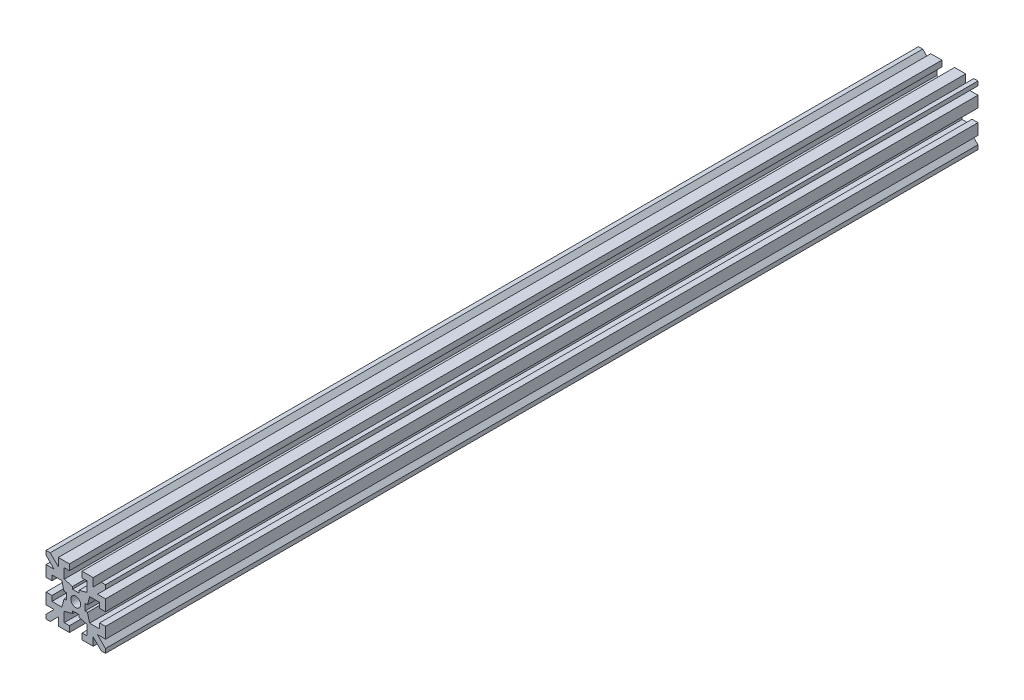
SolidWorks part; units mm, degrees
material "3.0205 (EN-AW 1200)"
ref_plane "Plano frontal" through (0, 0, 0) normal (0, 0, 1) x (1, 0, 0)
ref_plane "Plano superior" through (0, 0, 0) normal (0, 1, 0) x (1, 0, 0)
ref_plane "Plano direito" through (0, 0, 0) normal (1, 0, 0) x (0, 0, -1)
sketch "Esboço1" plane through (0, 0, 0) normal (0, 0, 1) x (1, 0, 0)
  line L0 (-25.7554, 0) -> (0, 0) construction
  line L1 (0, 0) -> (0, 21.5914) construction
  line L2 (0, 2.35) -> (-0.825, 2.35)
  line L3 (-0.825, 2.35) -> (-0.825, 2.95)
  line L4 (-0.825, 2.95) -> (-2.9, 3.5)
  line L5 (-2.9, 3.5) -> (-2.9, 6)
  line L6 (-2.9, 6) -> (-1.6, 6)
  line L7 (-1.6, 6) -> (-1.6, 7.5)
  line L8 (-1.6, 7.5) -> (-4.4, 7.5)
  line L9 (-4.4, 7.5) -> (-4.4, 5.4607)
  line L10 (-4.4, 5.4607) -> (-6.4393, 7.5)
  line L11 (-6.4393, 7.5) -> (-7.5, 7.5)
  line L12 (-7.5, 7.5) -> (0, 0) construction
  line L13 (-2.35, 0) -> (-2.35, 0.825)
  line L14 (-7.5, 6.4393) -> (-7.5, 7.5)
  line L15 (-5.4607, 4.4) -> (-7.5, 6.4393)
  line L16 (-7.5, 4.4) -> (-5.4607, 4.4)
  line L17 (-7.5, 1.6) -> (-7.5, 4.4)
  line L18 (-6, 1.6) -> (-7.5, 1.6)
  line L19 (-6, 2.9) -> (-6, 1.6)
  line L20 (-3.5, 2.9) -> (-6, 2.9)
  line L21 (-2.95, 0.825) -> (-3.5, 2.9)
  line L22 (-2.35, 0.825) -> (-2.95, 0.825)
  line L23 (-2.35, 0) -> (0, 0)
  line L24 (0, 0) -> (0, 2.35)
  dimension "D1" = 45
  dimension "D2" = 4.7
  dimension "D3" = 5.8
  dimension "D4" = 15
  dimension "D5" = 3.1
  dimension "D6" = 3.2
  dimension "D7" = 0.6
  dimension "D8" = 1.65
  dimension "D9" = 1.5
  dimension "D10" = 2.5
  dimension "D11" = 1.5
extrude "Ressalto-extrusão1" add sketch "Esboço1" along normal mid plane 220
mirror "Espelhar1" about plane through (0, 0, 0) normal (0, 1, 0) of "Ressalto-extrusão1"
mirror "Espelhar2" about plane through (0, 0, 0) normal (1, 0, 0) of "Espelhar1"
sketch "Esboço2" plane through (0, 0, 110) normal (0, 0, 1) x (1, 0, 0)
  circle A0 centre (0, 0) radius 1.25
  dimension "D1" = 2.5
extrude "Corte-extrusão1" cut sketch "Esboço2" against normal through all both and the other way through all
